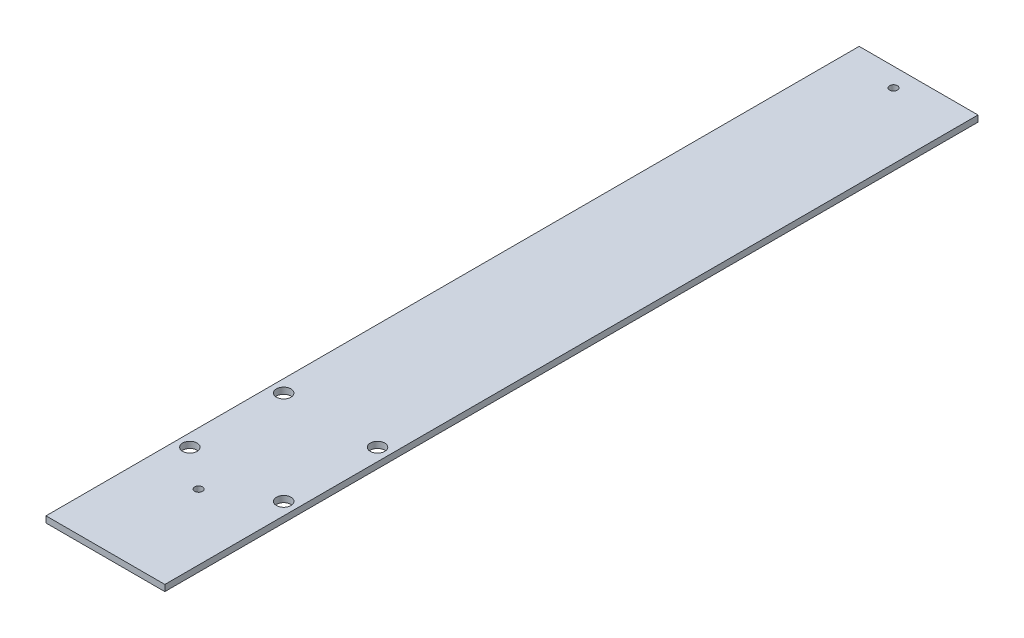
SolidWorks part; units mm, degrees
material "Alloy Steel"
ref_plane "Front" through (0, 0, 0) normal (0, 0, 1) x (1, 0, 0)
ref_plane "Top" through (0, 0, 0) normal (0, 1, 0) x (1, 0, 0)
ref_plane "Right" through (0, 0, 0) normal (1, 0, 0) x (0, 0, -1)
sketch "Sketch1" plane through (0, 0, 0) normal (0, 1, 0) x (1, 0, 0)
  line L1 (0, 0) -> (241.3, 0)
  line L2 (0, 0) -> (0, -1651)
  line L3 (0, -1651) -> (241.3, -1651)
  line L4 (241.3, 0) -> (241.3, -1651)
  dimension "D1" = 241.3
  dimension "D2" = 1651
extrude "Boss-Extrude1" add sketch "Sketch1" along normal blind 12.7
sketch "Sketch2" plane through (0, 12.7, 0) normal (0, 1, 0) x (1, 0, 0)
  line L0 (241.3, 0) -> (0, 0) construction
  line L1 (0, 0) -> (0, -1651) construction
  circle A0 centre (107.95, -38.1) radius 7.9375
  circle A1 centre (107.95, -1449.0573) radius 7.9375
  point P4 (0, 0)
  dimension "D1" = 15.875
  dimension "D2" = 15.875
  dimension "D3" = 1410.9573
  dimension "D4" = 38.1
  dimension "D5" = 107.95
extrude "Cut-Extrude1" cut sketch "Sketch2" against normal through all both and the other way through all
sketch "Sketch3" plane through (0, 0, 0) normal (0, -1, 0) x (1, 0, 0)
  circle A0 centre (215.9, 1193.8) radius 14.7295
  circle A1 centre (25.4, 1193.8) radius 14.7295
  circle A2 centre (25.4, 1384.3) radius 14.7295
  circle A3 centre (215.9, 1384.3) radius 14.7295
extrude "Cut-Extrude2" cut sketch "Sketch3" against normal through all
